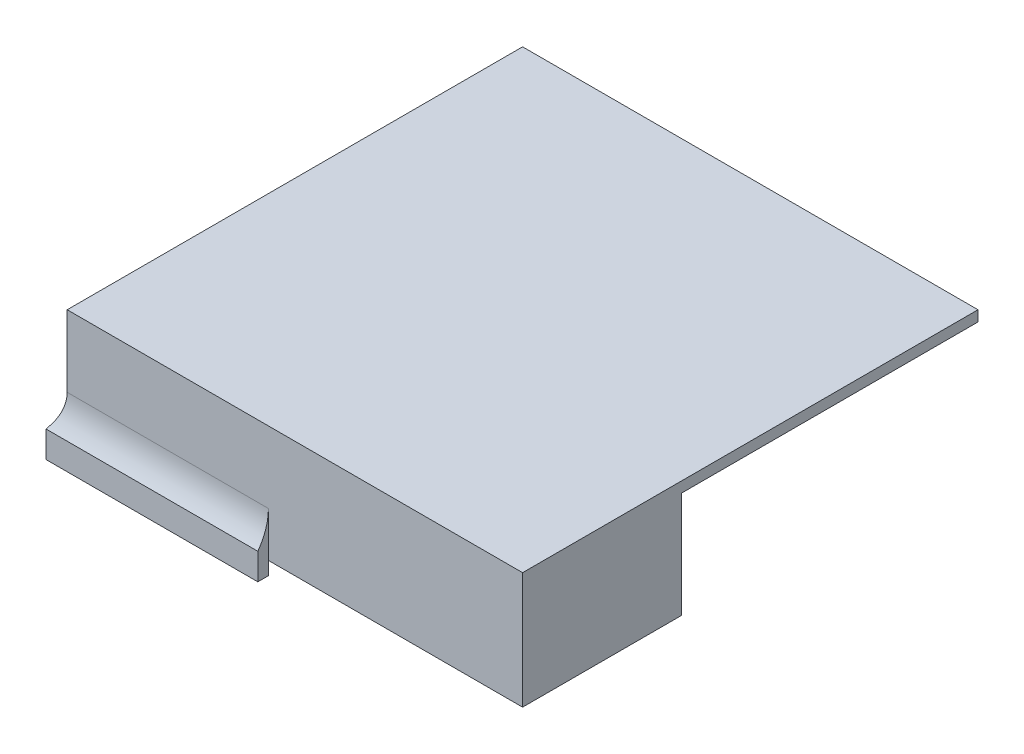
SolidWorks part; units mm, degrees
ref_plane "Front Plane" through (0, 0, 0) normal (0, 0, 1) x (1, 0, 0)
ref_plane "Top Plane" through (0, 0, 0) normal (0, 1, 0) x (1, 0, 0)
ref_plane "Right Plane" through (0, 0, 0) normal (1, 0, 0) x (0, 0, -1)
sketch "Sketch1" plane through (0, 0, 0) normal (0, 1, 0) x (1, 0, 0)
  line L0 (-43, -43) -> (14.9828, 14.9828)
  line L1 (43, 43) -> (-43, 43)
  line L2 (43, 43) -> (43, -43)
  line L3 (43, -43) -> (-43, -43)
  line L4 (-43, 43) -> (-43, -43)
  line L5 (43, 43) -> (-43, -43) construction
  line L6 (43, -43) -> (-43, 43) construction
  line L7 (-13.0345, 43) -> (43, -13.0345)
  point P0 (0, 0)
  point P10 (14.9828, 14.9828)
  dimension "D1" = 86
  dimension "D2" = 86
  dimension "D3" = 82
extrude "Boss-Extrude1" add sketch "Sketch1" along normal blind 20 contours L7 L1 L4 L0 | L7 L0 L3 L2 region at (-22.233, 0, -9.1252) region at (9.1252, 0, 22.233)
sketch "Sketch2" plane through (0, 20, 0) normal (0, 1, 0) x (1, 0, 0)
  line L0 (43, -43) -> (-43, -43) construction
  line L1 (43, 43) -> (-43, 43)
  line L2 (43, 43) -> (43, -43)
  line L3 (43, -43) -> (-43, -43)
  line L4 (-43, 43) -> (-43, -43)
  line L5 (43, 43) -> (-43, -43) construction
  line L6 (43, -43) -> (-43, 43) construction
  line L7 (-43, 43) -> (-43, -43) construction
  point P0 (0, 0)
extrude "Boss-Extrude2" add sketch "Sketch2" along normal blind 2
sketch "Sketch3" plane through (0, 0, 0) normal (0, -1, 0) x (1, 0, 0)
  line L10 (-13.8629, -41) -> (41, 13.8629)
  line L11 (41, 13.8629) -> (41, 41)
  line L12 (41, 41) -> (-41, 41)
  line L13 (-41, 41) -> (-41, -41)
  line L14 (-41, -41) -> (-13.8629, -41)
  line L15 (-13.8629, -41) -> (41, 13.8629)
  line L16 (41, 13.8629) -> (41, 41)
  line L17 (41, 41) -> (-41, 41)
  line L18 (-41, 41) -> (-41, -41)
  line L19 (-41, -41) -> (-13.8629, -41)
  dimension "D1" = 2
extrude "Cut-Extrude1" cut sketch "Sketch3" against normal blind 20
sketch "Sketch4" plane through (0, 0, 0) normal (0, -1, 0) x (1, 0, 0)
  line L9 (-43, 43) -> (-45, 43)
  line L10 (-43, 43) -> (-43, 3)
  line L11 (-43, 3) -> (-45, 3)
  line L12 (-45, 43) -> (-45, 3)
  line L13 (-45, 43) -> (-5, 43)
  line L14 (-45, 43) -> (-45, 45)
  line L15 (-45, 45) -> (-5, 45)
  line L16 (-5, 43) -> (-5, 45)
  line M13 (-43, 43) -> (-43, -43)
  dimension "D1" = 0
  dimension "D2" = 2
  dimension "D3" = 2
  dimension "D4" = 40
  dimension "D5" = 40
  dimension "D6" = 0
extrude "Boss-Extrude4" add sketch "Sketch4" along normal mid plane 5 contours L9 L12 L11 M13 | L15 L16 L13 L14 region at (-44, 0, 23)
fillet "Fillet1" radius 10 2 edges at (-43, 2.5, 23) (-24, 2.5, 43)
